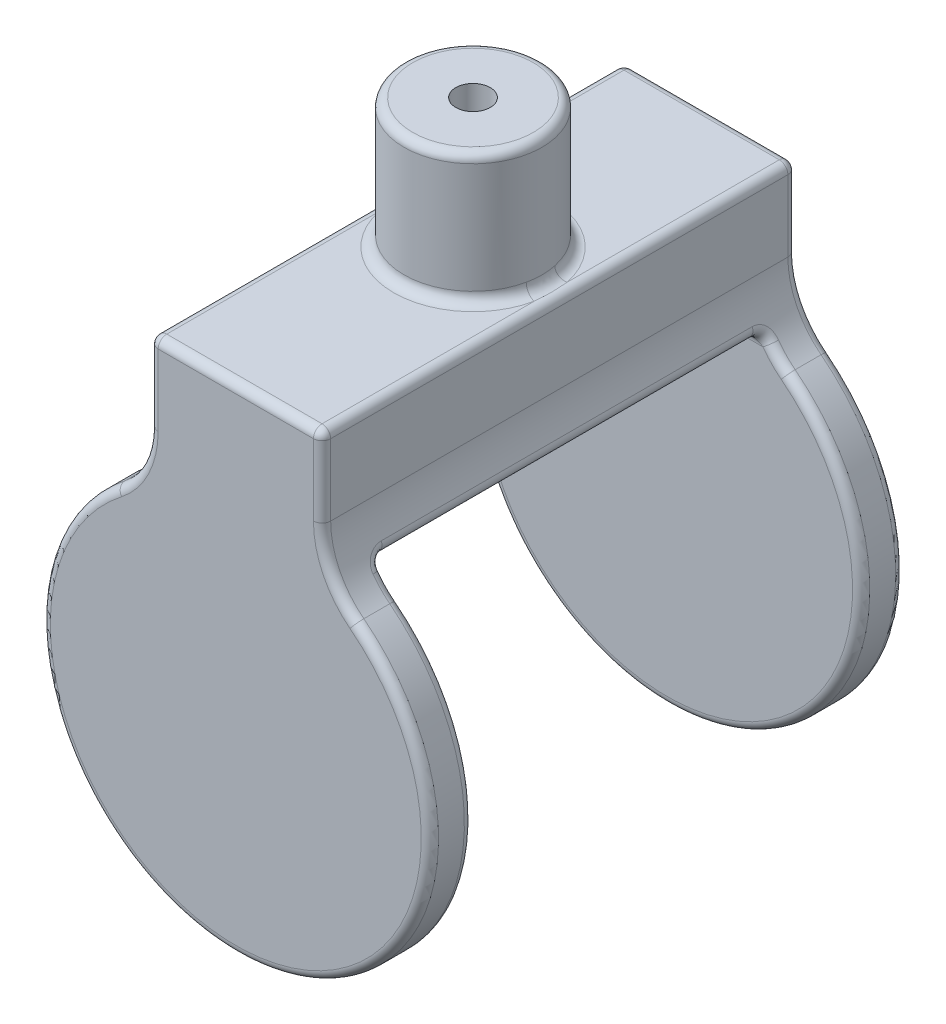
SolidWorks part; units mm, degrees
ref_plane "Front Plane" through (0, 0, 0) normal (0, 0, 1) x (1, 0, 0)
ref_plane "Top Plane" through (0, 0, 0) normal (0, 1, 0) x (1, 0, 0)
ref_plane "Right Plane" through (0, 0, 0) normal (1, 0, 0) x (0, 0, -1)
sketch "Sketch1" plane through (0, 0, 0) normal (0, 0, 1) x (1, 0, 0)
  line L0 (-10, 34.8852) -> (10, 34.8852)
  line L1 (-10, 20.1556) -> (-10, 34.8852)
  line L2 (0, 0) -> (0, 40.0954) construction
  line L3 (10, 20.1556) -> (10, 34.8852)
  arc A0 (-10, 20.1556) -> (10, 20.1556) centre (0, 0) ccw
  dimension "D1" = 45
  dimension "D2" = 10
  dimension "D3" = 20
  dimension "D4" = 10
  dimension "D5" = 34.8852
extrude "WholeBody" add sketch "Sketch1" along normal blind 55 contours L3 L0 L1 A0
ref_plane "Plane2" through (0, -22.5048, 0) normal (0, 1, 0) x (1, 0, 0)
sketch "Sketch2" plane through (0, -22.5048, 0) normal (0, 1, 0) x (1, 0, 0)
  line L0 (-22.5, -50) -> (22.5, -50)
  line L4 (22.5, -50) -> (22.5, -5)
  line L5 (-22.5, -50) -> (-22.5, -5)
  line L10 (-22.5, -5) -> (22.5, -5)
  line L11 (-10, -55) -> (10, -55) construction
  dimension "D1" = 22.5
  dimension "D2" = 22.5
  dimension "D3" = 5
extrude "Hole" cut sketch "Sketch2" along normal blind 42.66
fillet "Fillet1" radius 10 2 edges at (10, 20.1556, 27.5) (-10, 20.1556, 27.5)
fillet "Fillet2" radius 1 24 edges at (11.6235, 20.1552, 27.5) (-11.6235, 20.1552, 27.5) (10, 34.8852, 27.5) (-10, 34.8852, 27.5) (-12.6348, 18.8533, 50) (0, -22.5, 50) (12.6348, 18.8533, 50) (0, 20.1552, 50) (12.6348, 18.8533, 5) (0, -22.5, 5) (-12.6348, 18.8533, 5) (0, 20.1552, 5) (11.0128, 21.2321, 0) (10, 30.2513, 0) (0, 34.8852, 0) (-10, 30.2513, 0) (-11.0128, 21.2321, 0) (0, -22.5, 0) (0, 34.8852, 55) (10, 30.2513, 55) (11.0128, 21.2321, 55) (0, -22.5, 55) (-11.0128, 21.2321, 55) (-10, 30.2513, 55)
sketch "Sketch4" plane through (0, 34.8852, 0) normal (0, 1, 0) x (1, 0, 0)
  line L0 (0, 0) -> (0, -55) construction
  line L1 (9, -55) -> (-9, -55) construction
  line L2 (-9, -27.5) -> (9, -27.5) construction
  line L3 (-9, -1) -> (-9, -54) construction
  line L4 (9, -54) -> (9, -1) construction
  circle A0 centre (0, -27.5) radius 8
  dimension "D1" = 16
extrude "Boss-Extrude1" add sketch "Sketch4" along normal blind 15
fillet "Fillet3" radius 1.2 1 edges at (0, 34.8852, 35.5)
fillet "Fillet4" radius 1 1 edges at (0, 49.8852, 35.5)
sketch "Sketch5" plane through (0, 49.8852, 0) normal (0, 1, 0) x (1, 0, 0)
  circle A0 centre (0, -27.5) radius 2
  dimension "D1" = 4
extrude "Cut-Extrude1" cut sketch "Sketch5" against normal blind 7
